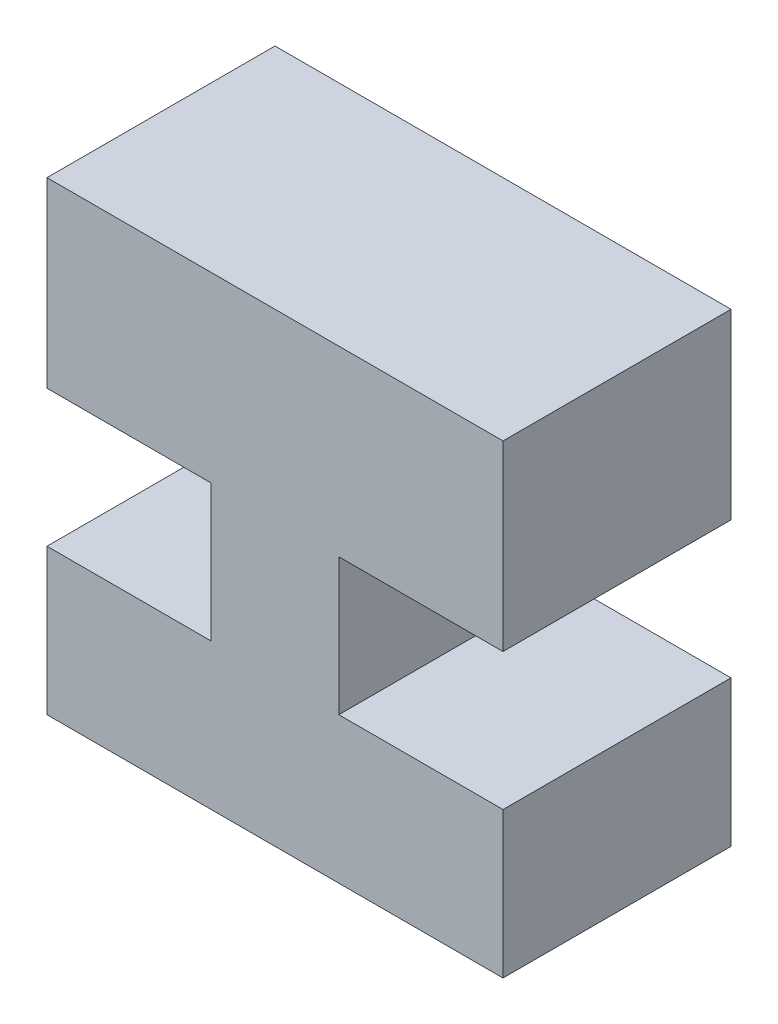
SolidWorks part; units mm, degrees
ref_plane "Front Plane" through (0, 0, 0) normal (0, 0, 1) x (1, 0, 0)
ref_plane "Top Plane" through (0, 0, 0) normal (0, 1, 0) x (1, 0, 0)
ref_plane "Right Plane" through (0, 0, 0) normal (1, 0, 0) x (0, 0, -1)
sketch "Sketch2" plane through (0, 0, 0) normal (0, 0, 1) x (1, 0, 0)
  line L0 (0, 0) -> (12.7, 0)
  line L1 (12.7, 0) -> (12.7, -5.08)
  line L2 (12.7, -5.08) -> (8.128, -5.08)
  line L3 (8.128, -5.08) -> (8.128, -8.89)
  line L4 (8.128, -8.89) -> (12.7, -8.89)
  line L5 (12.7, -8.89) -> (12.7, -12.954)
  line L6 (12.7, -12.954) -> (0, -12.954)
  line L7 (0, -12.954) -> (0, -8.89)
  line L8 (0, -8.89) -> (4.572, -8.89)
  line L9 (4.572, -8.89) -> (4.572, -5.08)
  line L10 (4.572, -5.08) -> (0, -5.08)
  line L11 (0, -5.08) -> (0, 0)
  dimension "D1" = 12.7
  dimension "D2" = 12.7
  dimension "D3" = 5.08
  dimension "D4" = 3.81
  dimension "D5" = 5.08
  dimension "D6" = 3.81
  dimension "D7" = 7.874
  dimension "D8" = 4.572
  dimension "D9" = 4.572
extrude "body" add sketch "Sketch2" along normal blind 6.35
ref_point "Point1"
sketch "Sketch4" plane through (0, -12.954, 0) normal (0, -1, 0) x (1, 0, 0)
  circle A0 centre (6.35, 3.175) radius 1.27
extrude "flag" add sketch "Sketch4" along normal blind 0.254
fillet "holder" radius 2.54 1 edges at (6.35, -12.954, 4.445)
